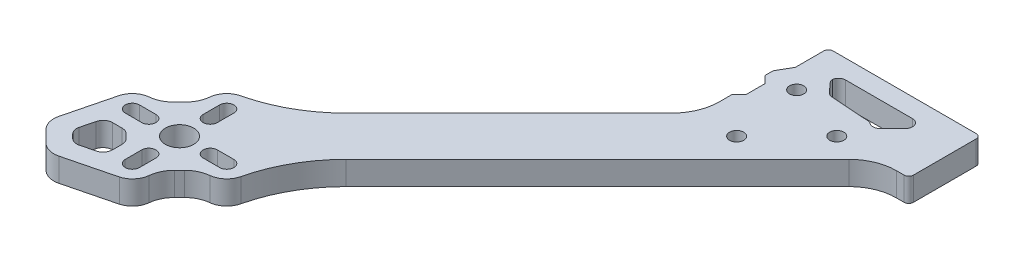
SolidWorks part; units mm, degrees
ref_plane "Front Plane" through (0, 0, 0) normal (0, 0, 1) x (1, 0, 0)
ref_plane "Top Plane" through (0, 0, 0) normal (0, 1, 0) x (1, 0, 0)
ref_plane "Right Plane" through (0, 0, 0) normal (1, 0, 0) x (0, 0, -1)
sketch "Sketch2" plane through (0, 0, 0) normal (0, 1, 0) x (1, 0, 0)
  line L0 (-39.4969, -89.7278) -> (17.9135, -32.3174)
  line L1 (9.4282, -17.0674) -> (9.4282, -32.3174) construction
  line L2 (9.4282, -32.3174) -> (24.6782, -32.3174) construction
  line L3 (-54.6599, -87.9202) -> (-9.3218, -42.5821)
  line L4 (-9.3218, -37.0674) -> (-9.3218, -42.5821)
  line L5 (9.4282, -32.3174) -> (24.6782, -17.0674) construction
  line L6 (-7.596, -17.0674) -> (24.6782, -17.0674)
  line L7 (-9.3218, -37.0674) -> (-9.3218, -17.0674)
  line L8 (24.6782, -17.0674) -> (24.6782, -32.3174)
  line L9 (9.4282, -17.0674) -> (-9.3218, -17.0674) construction
  line L10 (24.6782, -32.3174) -> (17.9135, -32.3174)
  line L13 (9.4282, -32.3174) -> (-14.0521, -55.7977) construction
  line L15 (-1.4599, -22.796) -> (1.0821, -25.5753)
  line L16 (1.0821, -25.5753) -> (10.2725, -26.2276)
  line L17 (10.2725, -26.2276) -> (11.7409, -27.1763)
  line L18 (9.4282, -17.0674) -> (24.6782, -17.0674) construction
  line L19 (24.6782, -32.3174) -> (24.6782, -17.0674) construction
  line L20 (13.4592, -28.2864) -> (13.2093, -28.125)
  line L21 (-60.1746, -101.9202) -> (-43.2974, -101.9202) construction
  line L22 (17.8498, -21.0674) -> (-1.4599, -21.0674)
  line L23 (-1.4599, -21.0674) -> (-1.4599, -22.796)
  line L24 (-14.0521, -55.7977) -> (-60.1746, -101.9202) construction
  line L25 (-60.1746, -101.9202) -> (-60.1746, -85.2433) construction
  line L26 (11.7409, -27.1763) -> (17.8498, -21.0674)
  line L27 (-60.1746, -101.9202) -> (-75.0152, -101.9202) construction
  line L28 (-60.1746, -101.9202) -> (-60.1746, -117.9623) construction
  line L29 (-7.596, -24.0674) -> (-9.326, -27.0674)
  line L30 (-53.6746, -101.9202) -> (-50.1746, -101.9202) construction
  line L31 (-7.596, -24.0674) -> (-7.596, -17.0674)
  line L32 (-53.6746, -100.4202) -> (-50.1746, -100.4202)
  line L33 (-53.6746, -103.4202) -> (-50.1746, -103.4202)
  line L34 (-60.1746, -108.4202) -> (-60.1746, -111.9202) construction
  line L35 (-58.6746, -108.4202) -> (-58.6746, -111.9202)
  line L36 (-61.6746, -108.4202) -> (-61.6746, -111.9202)
  line L37 (-66.6746, -101.9202) -> (-70.1746, -101.9202) construction
  line L38 (-66.6746, -103.4202) -> (-70.1746, -103.4202)
  line L39 (-66.6746, -100.4202) -> (-70.1746, -100.4202)
  line L40 (-60.1746, -95.4202) -> (-60.1746, -91.9202) construction
  line L41 (-61.6746, -95.4202) -> (-61.6746, -91.9202)
  line L42 (-58.6746, -95.4202) -> (-58.6746, -91.9202)
  line L43 (-70.1746, -97.9202) -> (-64.1746, -97.9202)
  line L44 (-64.1746, -91.9202) -> (-64.1746, -97.9202)
  line L45 (-56.1746, -111.9202) -> (-56.1746, -105.9202)
  line L46 (-50.1746, -105.9202) -> (-56.1746, -105.9202)
  line L47 (-77.1452, -113.2339) -> (-71.4883, -118.8908)
  line L48 (-39.4969, -89.7278) -> (-46.1894, -96.4203)
  line L49 (-60.1746, -87.9202) -> (-54.6599, -87.9202)
  line L50 (-46.1746, -101.9202) -> (-46.1894, -96.4203)
  line L51 (-71.4883, -118.8908) -> (-59.0474, -115.7581)
  line L52 (-77.1452, -113.2339) -> (-74.0537, -100.9444)
  line L53 (-72.7126, -112.0096) -> (-70.2645, -114.4577)
  line L54 (-70.2645, -114.4577) -> (-64.7708, -113.0744)
  line L55 (-64.7708, -113.0744) -> (-64.7708, -108.6377)
  line L56 (-64.7708, -108.6377) -> (-66.8921, -106.5164)
  line L57 (-66.8921, -106.5164) -> (-71.3308, -106.5164)
  line L58 (-71.3308, -106.5164) -> (-72.7126, -112.0096)
  line L59 (-72.7126, -112.0096) -> (-72.6759, -112.0237)
  circle A0 centre (-60.1746, -101.9202) radius 3
  circle A1 centre (-60.1746, -101.9202) radius 5 construction
  circle A2 centre (9.4282, -32.3174) radius 1.5
  arc A3 (-53.6746, -100.4202) -> (-53.6746, -103.4202) centre (-53.6746, -101.9202) ccw
  circle A4 centre (-60.1746, -101.9202) radius 12 construction
  arc A5 (-50.1746, -103.4202) -> (-50.1746, -100.4202) centre (-50.1746, -101.9202) ccw
  circle A6 centre (-1.1784, -42.924) radius 1.5
  arc A7 (-58.6746, -108.4202) -> (-61.6746, -108.4202) centre (-60.1746, -108.4202) ccw
  arc A8 (-61.6746, -111.9202) -> (-58.6746, -111.9202) centre (-60.1746, -111.9202) ccw
  arc A9 (-66.6746, -103.4202) -> (-66.6746, -100.4202) centre (-66.6746, -101.9202) ccw
  arc A10 (-70.1746, -100.4202) -> (-70.1746, -103.4202) centre (-70.1746, -101.9202) ccw
  arc A11 (-61.6746, -95.4202) -> (-58.6746, -95.4202) centre (-60.1746, -95.4202) ccw
  arc A12 (-58.6746, -91.9202) -> (-61.6746, -91.9202) centre (-60.1746, -91.9202) ccw
  arc A13 (-60.1746, -87.9202) -> (-64.1746, -91.9202) centre (-60.1746, -91.9202) ccw
  arc A14 (-50.1746, -105.9202) -> (-46.1746, -101.8987) centre (-50.1746, -101.9202) ccw
  circle A16 centre (-3.3218, -28.0674) radius 1.5
  arc A17 (-70.1746, -97.9202) -> (-74.0537, -100.9444) centre (-70.1746, -101.9202) ccw
  arc A18 (-59.0474, -115.7581) -> (-56.1746, -111.9202) centre (-60.1746, -111.9202) ccw
  point P36 (-51.9246, -101.9202)
  point P41 (-51.9246, -103.4202)
  point P47 (-60.1746, -110.1702)
  point P54 (-68.4246, -101.9202)
  point P63 (-60.1746, -93.6702)
  point P70 (-60.1746, -101.9202)
  dimension "D4" = 3
  dimension "D5" = 15.0104
  dimension "D9" = 3
  dimension "D24" = 8
  dimension "D25" = 8
  dimension "D2" = 3
  dimension "D15" = 6
  dimension "D16" = 10
  dimension "D17" = 24
  dimension "D18" = 3
  dimension "D21" = 4
  dimension "D22" = 8
  dimension "D23" = 4
  dimension "D35" = 4
  dimension "D6" = 45
  dimension "D7" = 13.4397
  dimension "D8" = 12
  dimension "D10" = 15
  dimension "D11" = 6
  dimension "D12" = 4
  dimension "D13" = 4
  dimension "D14" = 120
  dimension "D19" = 6.5
  dimension "D20" = 3.5
  dimension "D26" = 8
  dimension "D27" = 4
  dimension "D28" = 20
  dimension "D29" = 8
  dimension "D30" = 1.5
  dimension "D31" = 3
  dimension "D32" = 3
  dimension "D33" = 4
  dimension "D34" = 4
extrude "Boss-Extrude1" add sketch "Sketch2" along normal blind 5 contours L31 L29 L7 L4 L3 L0 L10 L8 L6 A16 A6 A2 L23 L22 L17 L16 L15 region at (-23.0581, 0, 62.7579)
fillet "Fillet1" radius 1.5 6 edges at (10.2725, 2.5, 26.2276) (1.0821, 2.5, 25.5753) (-1.4599, 2.5, 22.796) (-1.4599, 2.5, 21.0674) (11.7409, 2.5, 27.1763) (17.8498, 2.5, 21.0674)
fillet "Fillet3" radius 10 1 edges at (17.9135, 2.5, 32.3174)
fillet "Fillet5" radius 10 1 edges at (-9.3218, 2.5, 42.5821)
chamfer "Chamfer1" distance 4.5 angle 45 2 edges at (-64.1746, 2.5, 97.9202) (-56.1746, 2.5, 105.9202)
fillet "Fillet6" radius 6 4 edges at (-64.1746, 2.5, 93.4202) (-68.6746, 2.5, 97.9202) (-56.1746, 2.5, 110.4202) (-51.6746, 2.5, 105.9202)
fillet "Fillet7" radius 4 2 edges at (-71.4883, 2.5, 118.8908) (-77.1452, 2.5, 113.2339)
fillet "Fillet8" radius 2 6 edges at (-71.3308, 2.5, 106.5164) (-66.8921, 2.5, 106.5164) (-64.7708, 2.5, 108.6377) (-64.7708, 2.5, 113.0744) (-70.2645, 2.5, 114.4577) (-72.7126, 2.5, 112.0096)
fillet "Fillet9" radius 30 2 edges at (-54.6599, 2.5, 87.9202) (-46.1894, 2.5, 96.4203)
sketch "Sketch3" plane through (0, 5, 0) normal (0, 1, 0) x (1, 0, 0)
  circle A0 centre (-60.1746, -101.9202) radius 62.5
  dimension "D1" = 125
sketch "Sketch4" plane through (0, 5, 0) normal (0, 1, 0) x (1, 0, 0)
  line L0 (-9.3218, -28.82) -> (-7.8218, -30.32)
  line L1 (-9.3218, -38.44) -> (-9.3218, -27.0601) construction
  line L2 (-7.8218, -30.32) -> (-7.8218, -34.32)
  line L3 (-7.8218, -34.32) -> (-9.3218, -35.82)
  line L4 (-9.3218, -28.82) -> (-9.3218, -35.82)
  dimension "D1" = 135
  dimension "D2" = 135
  dimension "D3" = 1.5
  dimension "D4" = 4
  dimension "D5" = 4.12
extrude "Cut-Extrude1" cut sketch "Sketch4" against normal through all contours L0 L4 L3 L2 region at (-8.64, 5, 32.32)
fillet "Fillet10" radius 1 3 edges at (-7.596, 2.5, 17.0674) (24.6782, 2.5, 32.3174) (24.6782, 2.5, 17.0674)
